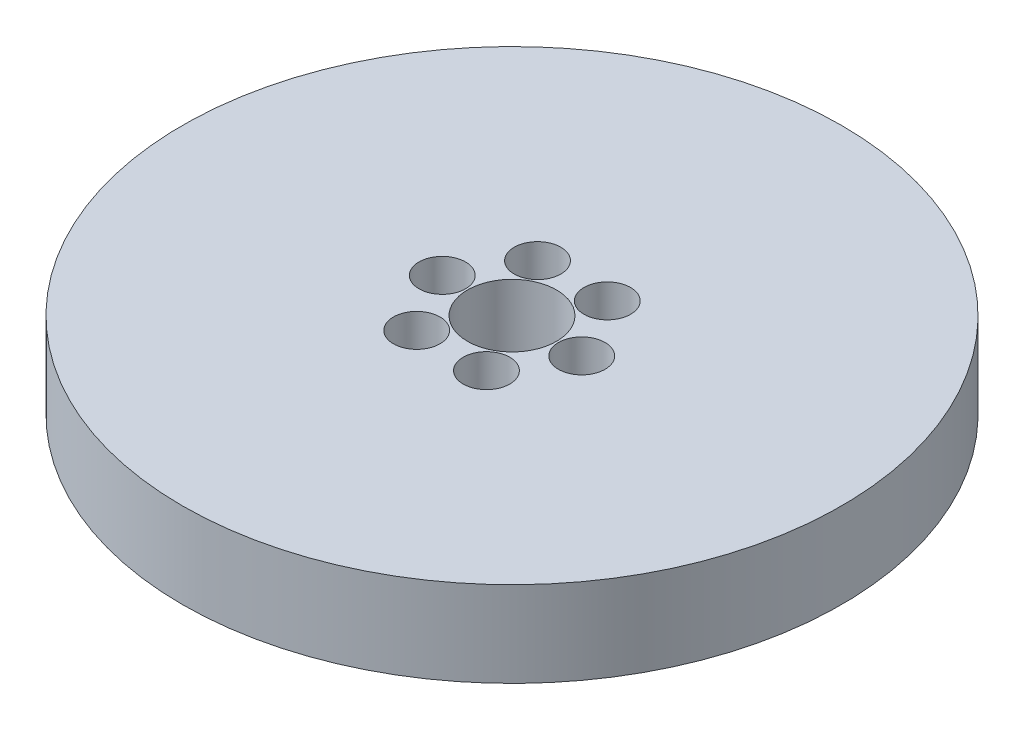
SolidWorks part; units mm, degrees
ref_plane "Front Plane" through (0, 0, 0) normal (0, 0, 1) x (1, 0, 0)
ref_plane "Top Plane" through (0, 0, 0) normal (0, 1, 0) x (1, 0, 0)
ref_plane "Right Plane" through (0, 0, 0) normal (1, 0, 0) x (0, 0, -1)
sketch "Sketch1" plane through (0, 0, 0) normal (0, 1, 0) x (1, 0, 0)
  circle A0 centre (0, 0) radius 92.5
  dimension "FLANGE_OD" = 185
extrude "Boss-Extrude1" add sketch "Sketch1" along normal blind 24
sketch "Sketch2" plane through (0, 0, 0) normal (0, 1, 0) x (1, 0, 0)
  circle A0 centre (0, 0) radius 12.5
  dimension "BORE_D" = 25
extrude "Cut-Extrude1" cut sketch "Sketch2" along normal through all
sketch "Sketch3" plane through (0, 24, 0) normal (0, 1, 0) x (1, 0, 0)
  circle A0 centre (0, 0) radius 19.5764 construction
  circle A1 centre (-19.5764, 0) radius 6.5386
  dimension "BOLT_D" = 13.0772
  dimension "BOLT_PCD" = 39.1529
extrude "Cut-Extrude2" cut sketch "Sketch3" against normal blind 18.4098
pattern_circular "CirPattern1" count 6 over 360 about axis through (0, 0, 0) along (0, 1, 0) of "Cut-Extrude2"
